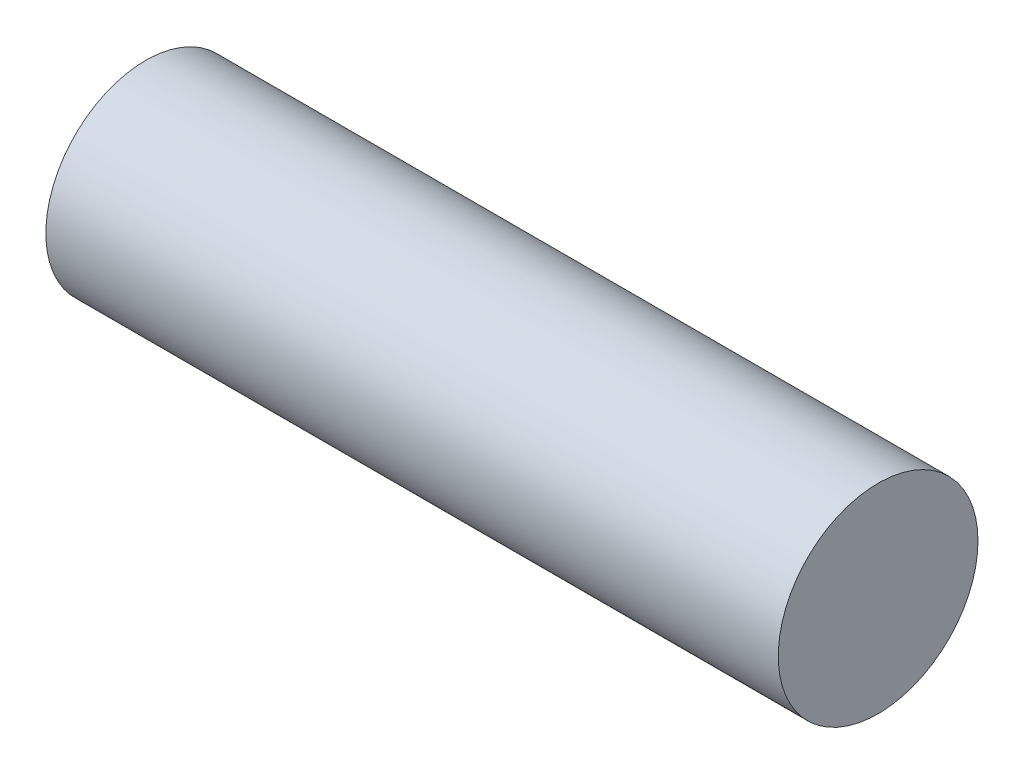
SolidWorks part; units mm, degrees
ref_plane "前视基准面" through (0, 0, 0) normal (0, 0, 1) x (1, 0, 0)
ref_plane "上视基准面" through (0, 0, 0) normal (0, 1, 0) x (1, 0, 0)
ref_plane "右视基准面" through (0, 0, 0) normal (1, 0, 0) x (0, 0, -1)
sketch "草图1" plane through (0, 0, 0) normal (1, 0, 0) x (0, 0, -1)
  circle A0 centre (0, 0) radius 1.5
  dimension "D1" = 3
extrude "凸台-拉伸1" add sketch "草图1" along normal blind 11
